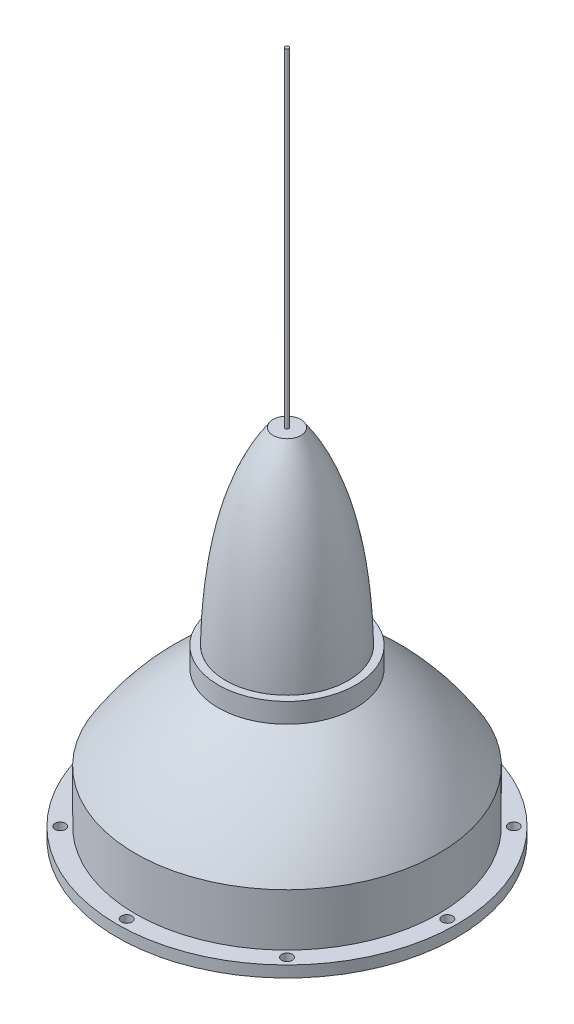
SolidWorks part; units mm, degrees
ref_plane "Front Plane" through (0, 0, 0) normal (0, 0, 1) x (1, 0, 0)
ref_plane "Top Plane" through (0, 0, 0) normal (0, 1, 0) x (1, 0, 0)
ref_plane "Right Plane" through (0, 0, 0) normal (1, 0, 0) x (0, 0, -1)
sketch "Sketch1" plane through (0, 0, 0) normal (0, 0, 1) x (1, 0, 0)
  line L0 (0, 0) -> (0, 32.5571)
  line L1 (0, 0) -> (45, 0)
  line L3 (0, 32.5571) -> (16.2196, 32.5571)
  spline S0 degree 3 poles (16.2196, 32.5571) (28.7671, 24.9752) (38.3606, 14.1229) (45, 0) knots 0.282785 0.282785 0.282785 0.282785 1 1 1 1
  dimension "D1" = 45
revolve "Revolve1" add sketch "Sketch1" angle 360 about L0
sketch "Sketch2" plane through (0, 0, 0) normal (0, 0, 1) x (1, 0, 0)
  line L0 (0, 0) -> (45, 0) construction
  line L2 (16.2196, 32.5571) -> (16.2196, 29.2464)
  line L3 (16.2196, 32.5571) -> (0, 32.5571)
  line L4 (0, 32.5571) -> (0, 0)
  line L5 (0, 0) -> (40.4481, 0)
  spline S0 degree 3 poles (40.4481, 0) (34.9985, 12.0781) (26.9224, 21.8269) (16.2196, 29.2464) knots 0 0 0 0 0.864736 0.864736 0.864736 0.864736
revolve "Cut-Revolve1" cut sketch "Sketch2" angle 360 about L0
ref_plane "Plane1" through (0, 0, 0) normal (0, -1, 0) x (-1, 0, 0)
sketch "Sketch3" plane through (0, 0, 0) normal (0, -1, 0) x (-1, 0, 0)
  circle A3 centre (0, 0) radius 37.3594
  circle A4 centre (0, 0) radius 45
extrude "Boss-Extrude2" add sketch "Sketch3" against normal blind 6
ref_plane "Plane2" through (0, 0, 0) normal (0, -1, 0) x (-1, 0, 0)
sketch "Sketch4" plane through (0, 0, 0) normal (0, -1, 0) x (-1, 0, 0)
  circle A0 centre (-42.5, 0) radius 1.4
  circle A1 centre (-30.052, -30.052) radius 1.4
  circle A2 centre (0, -42.5) radius 1.4
  circle A3 centre (30.052, -30.052) radius 1.4
  circle A4 centre (42.5, 0) radius 1.4
  circle A5 centre (30.052, 30.052) radius 1.4
  circle A6 centre (0, 42.5) radius 1.4
  circle A7 centre (-30.052, 30.052) radius 1.4
ref_plane "Plane3" through (0, 6, 0) normal (0, -1, 0) x (-1, 0, 0)
sketch "Sketch6" plane through (0, 6, 0) normal (0, -1, 0) x (-1, 0, 0)
  circle A0 centre (0, 0) radius 40.1838
  circle A1 centre (0, 0) radius 41.8898
extrude "Cut-Extrude1" cut sketch "Sketch6" against normal blind 5
sketch "Sketch7" plane through (0, 0, 0) normal (0, -1, 0) x (-1, 0, 0)
  circle A0 centre (0, 0) radius 47
  circle A1 centre (0, 0) radius 37.3594
extrude "Boss-Extrude4" add sketch "Sketch7" against normal blind 6
extrude "Cut-Extrude2" cut sketch "Sketch4" against normal blind 6
sketch "Sketch8" plane through (0, 0, 0) normal (0, -1, 0) x (-1, 0, 0)
  circle A0 centre (0, 0) radius 45
  circle A1 centre (0, 0) radius 47
extrude "Cut-Extrude3" cut sketch "Sketch8" against normal blind 10
sketch "Sketch9" plane through (0, 0, 0) normal (0, -1, 0) x (-1, 0, 0)
  circle A0 centre (0, 0) radius 37.3594
  circle A1 centre (0, 0) radius 45
extrude "Cut-Extrude4" cut sketch "Sketch9" against normal blind 4
ref_plane "Plane4" through (0, 32.5571, 0) normal (0, 1, 0) x (1, 0, 0)
sketch "Sketch10" plane through (0, 32.5571, 0) normal (0, 1, 0) x (1, 0, 0)
  circle A0 centre (0, 0) radius 16.2196
  circle A1 centre (0, 0) radius 18.2196
  dimension "D1" = 2
extrude "Boss-Extrude5" add sketch "Sketch10" along normal blind 4 and the other way blind 3
extrude "Boss-Extrude6" add sketch "Sketch9<2>" along normal blind 8 and the other way blind 5
sketch "Sketch9<2>" plane through (0, 0, 0) normal (0, -1, 0) x (-1, 0, 0) same geometry as "Sketch9"
ref_plane "Plane5" through (0, 6, 0) normal (0, 1, 0) x (1, 0, 0)
sketch "Sketch13" plane through (0, 6, 0) normal (0, 1, 0) x (1, 0, 0)
  circle A0 centre (0, 0) radius 40.1838
  circle A1 centre (0, 0) radius 45
extrude "Cut-Extrude5" cut sketch "Sketch13" against normal blind 11
extrude "Cut-Extrude6" cut sketch "Sketch4<2>" along normal blind 10
sketch "Sketch4<2>" plane through (0, 0, 0) normal (0, -1, 0) x (-1, 0, 0) same geometry as "Sketch4"
ref_plane "Plane6" through (0, 36.5571, 0) normal (0, 1, 0) x (1, 0, 0)
sketch "Sketch15" plane through (0, 0, 0) normal (0, 0, 1) x (1, 0, 0)
  line L1 (20.0415, 36.5571) -> (-20.0415, 36.5571) construction
  line L5 (0, 36.5571) -> (0, 86.5571)
  line L6 (0, 86.5571) -> (3.67, 86.5571)
  line L7 (16.2196, 36.5571) -> (0, 36.5571)
  line L8 (0, 36.5571) -> (16.2196, 36.5571)
  line L9 (16.2196, 36.5571) -> (16.2196, 86.5571)
  line L11 (16.2196, 86.5571) -> (3.67, 86.5571)
  spline S0 degree 2 poles (3.67, 86.5571) (15.6355, 69.8891) (16.2196, 36.5571) knots 0 0 0 1 1 1
revolve "Revolve2" add sketch "Sketch15" angle 360 about L5
ref_plane "Plane7" through (0, 86.5571, 0) normal (0, 1, 0) x (1, 0, 0)
sketch "Sketch16" plane through (0, 86.5571, 0) normal (0, 1, 0) x (1, 0, 0)
  circle A0 centre (0, 0) radius 0.5
extrude "Boss-Extrude8" add sketch "Sketch16" along normal blind 87.2
